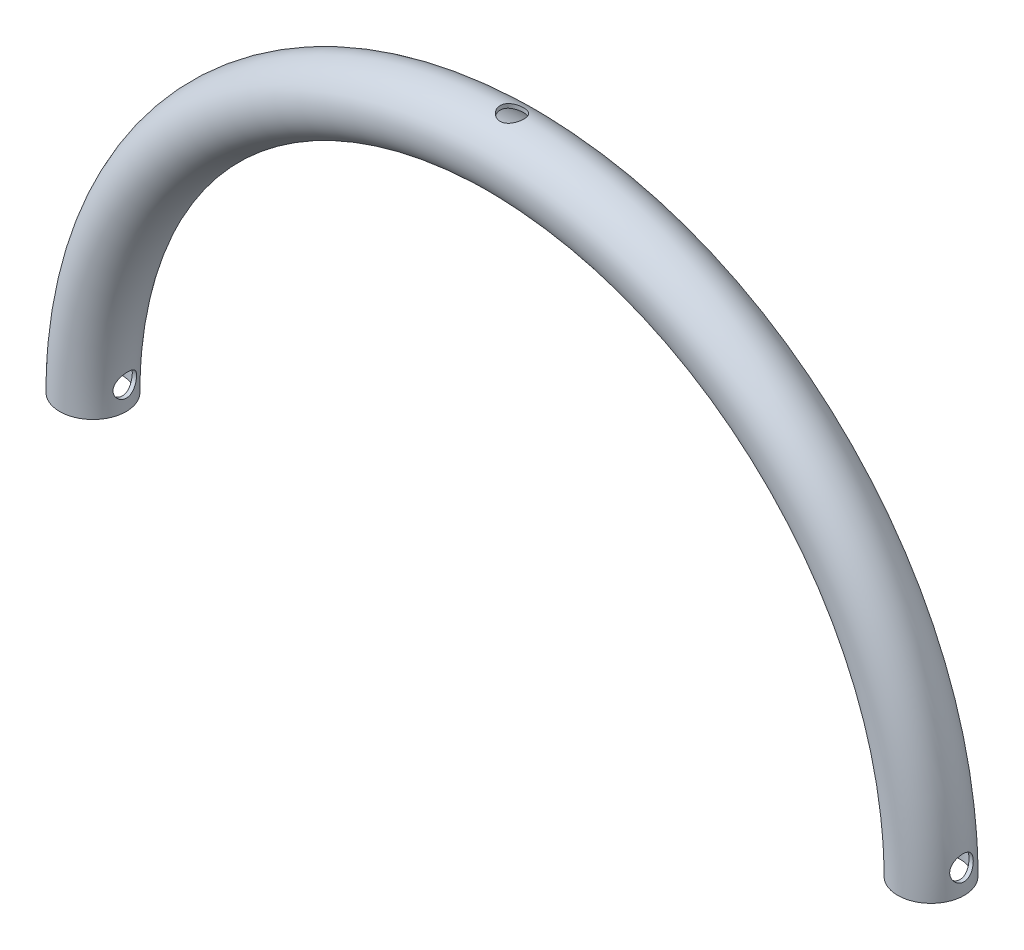
SolidWorks part; units mm, degrees
material "Galvanized Steel"
ref_plane "Front Plane" through (0, 0, 0) normal (0, 0, 1) x (1, 0, 0)
ref_plane "Top Plane" through (0, 0, 0) normal (0, 1, 0) x (1, 0, 0)
ref_plane "Right Plane" through (0, 0, 0) normal (1, 0, 0) x (0, 0, -1)
sketch "Sketch1" plane through (0, 0, 0) normal (0, 1, 0) x (1, 0, 0)
  circle A0 centre (0, 0) radius 7.8994
  circle A1 centre (0, 0) radius 8.9662
sketch "Sketch2" plane through (0, 0, 0) normal (0, 0, 1) x (1, 0, 0)
  arc A0 (0, 0) -> (226.06, 0) centre (113.03, 0) cw
sweep "Sweep1" add profiles "Sketch1" path "Sketch2"
sketch "Sketch3" plane through (0, 0, 0) normal (1, 0, 0) x (0, 0, -1)
  line L0 (-8.9662, 0) -> (8.9662, 0) construction
  circle A0 centre (0, 6.35) radius 3.175
  dimension "D1" = 6.35
extrude "Cut-Extrude1" cut sketch "Sketch3" against normal through all and the other way through all
sketch "Sketch5" plane through (0, 0, 0) normal (0, 0, 1) x (1, 0, 0)
  line L0 (113.03, 0) -> (113.03, 155.7767) construction
sketch "Sketch6" plane through (0, 0, 0) normal (0, 1, 0) x (1, 0, 0)
  circle A0 centre (113.03, 0) radius 3.175
extrude "Cut-Extrude4" cut sketch "Sketch6" against normal blind 2.54 and the other way through all
